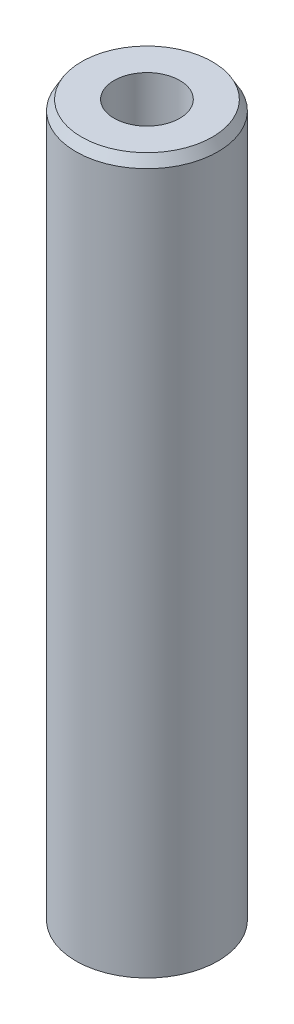
SolidWorks part; units mm, degrees
ref_plane "Front Plane" through (0, 0, 0) normal (0, 0, 1) x (1, 0, 0)
ref_plane "Top Plane" through (0, 0, 0) normal (0, 1, 0) x (1, 0, 0)
ref_plane "Right Plane" through (0, 0, 0) normal (1, 0, 0) x (0, 0, -1)
sketch "Sketch1" plane through (0, 0, 0) normal (0, 1, 0) x (1, 0, 0)
  circle A0 centre (0, 0) radius 12.5
  dimension "SHAFT_OD" = 25
extrude "Boss-Extrude1" add sketch "Sketch1" along normal blind 126.0508
sketch "Sketch2" plane through (0, 0, 0) normal (0, 1, 0) x (1, 0, 0)
  circle A0 centre (0, 0) radius 5.7757
  dimension "BORE_D" = 11.5514
extrude "Cut-Extrude1" cut sketch "Sketch2" along normal through all
chamfer "Chamfer1" distance 1.7324 angle 30 2 edges at (0, 126.0508, 12.5) (0, 0, 12.5) first distance on face at (0, 126.0508, 12.5) first distance on face at (0, 0, 5.7757)
